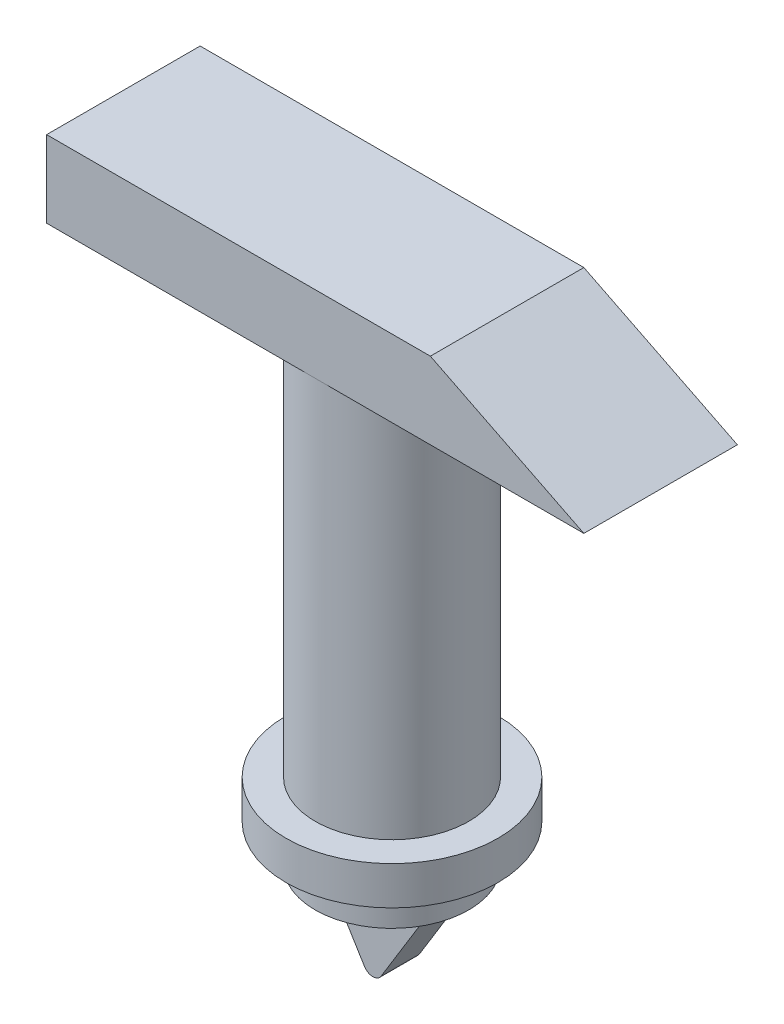
SolidWorks part; units mm, degrees
ref_plane "Alzado" through (0, 0, 0) normal (0, 0, 1) x (1, 0, 0)
ref_plane "Planta" through (0, 0, 0) normal (0, 1, 0) x (1, 0, 0)
ref_plane "Vista lateral" through (0, 0, 0) normal (1, 0, 0) x (0, 0, -1)
sketch "Croquis2" plane through (0, 0, 0) normal (0, 1, 0) x (1, 0, 0)
  circle A0 centre (0, 0) radius 10
  dimension "D1" = 20
extrude "Saliente-Extruir1" add sketch "Croquis2" along normal mid plane 60
sketch "Croquis3" plane through (0, 0, 0) normal (0, 0, 1) x (1, 0, 0)
  line L0 (0, -30) -> (0, -40) construction
  line L1 (-10, -30) -> (10, -30) construction
  line L2 (-1.0827, -40.6638) -> (-7.62, -30)
  line L3 (1.0827, -40.6638) -> (7.62, -30)
  line L4 (-7.62, -30) -> (7.62, -30)
  arc A0 (-1.0827, -40.6638) -> (1.0827, -40.6638) centre (0, -40) ccw
  dimension "D1" = 2.54
  dimension "D2" = 10
  dimension "D3" = 7.62
extrude "Saliente-Extruir2" add sketch "Croquis3" along normal mid plane 5
sketch "Croquis4" plane through (0, 0, 0) normal (0, 0, 1) x (1, 0, 0)
  line L0 (10, -30) -> (10, 30) construction
  line L1 (10, -20) -> (13.81, -20)
  line L2 (10, -20) -> (10, -25)
  line L3 (10, -25) -> (13.81, -25)
  line L4 (13.81, -20) -> (13.81, -25)
  line L5 (-10, -30) -> (10, -30) construction
  line L6 (0, -30) -> (0, -94.016) construction
  line L7 (7.62, -30) -> (-7.62, -30) construction
  dimension "D1" = 3.81
  dimension "D2" = 5
  dimension "D3" = 5
revolve "Revolución1" add sketch "Croquis4" angle 360 about L6
sketch "Croquis5" plane through (0, 30, 0) normal (0, 1, 0) x (1, 0, 0)
  line L1 (35, 10) -> (-35, 10)
  line L2 (35, 10) -> (35, -10)
  line L3 (35, -10) -> (-35, -10)
  line L4 (-35, 10) -> (-35, -10)
  point P4 (0, -10)
  point P5 (-35, 0)
  dimension "D1" = 20
  dimension "D2" = 70
extrude "Saliente-Extruir3" add sketch "Croquis5" along normal blind 10
sketch "Croquis6" plane through (0, 0, 10) normal (0, 0, 1) x (1, 0, 0)
  line L0 (35, 30) -> (15, 40)
  line L1 (-35, 40) -> (35, 40) construction
  line L2 (15, 40) -> (35, 40)
  line L3 (35, 40) -> (35, 30) construction
  line L4 (35, 40) -> (35, 30)
  dimension "D1" = 20
extrude "Cortar-Extruir1" cut sketch "Croquis6" against normal blind 20
ref_axis "Eje1" through (0, 30, 0) along (0, -1, 0)
